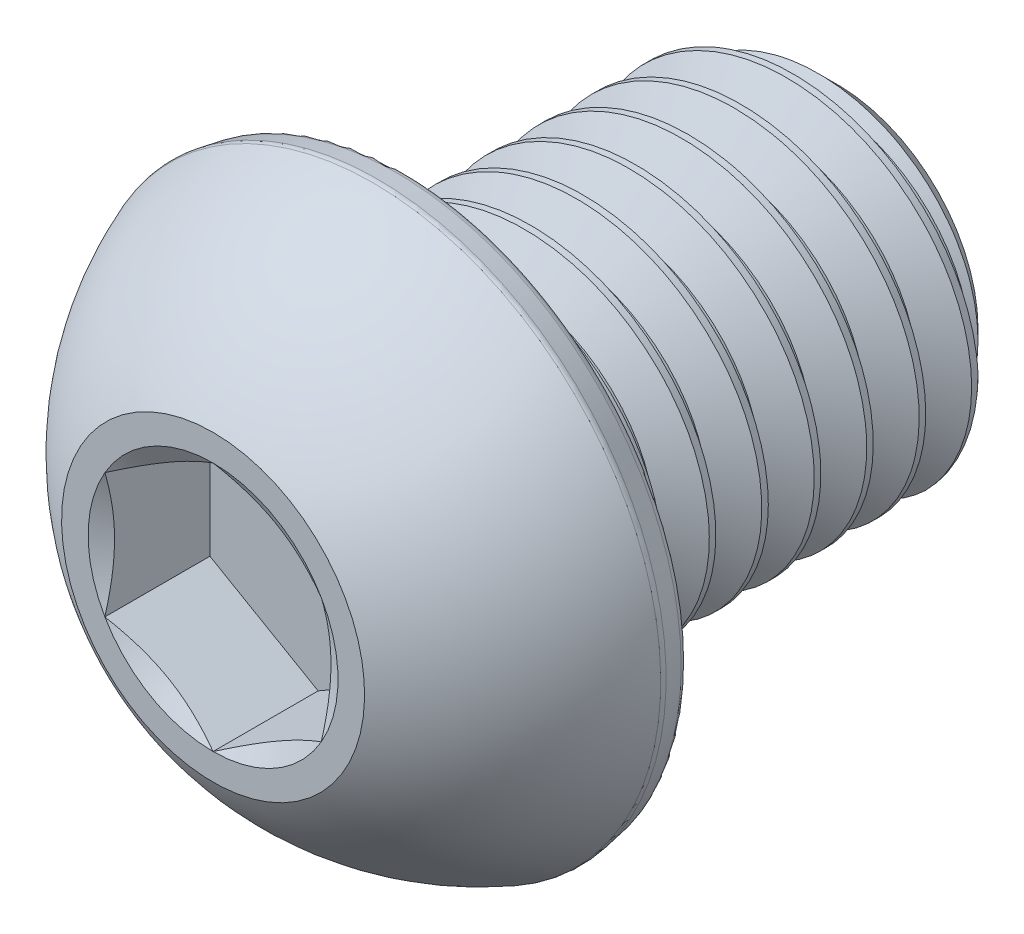
SolidWorks part; units mm, degrees
ref_plane "Front Plane" through (0, 0, 0) normal (0, 0, 1) x (1, 0, 0)
ref_plane "Top Plane" through (0, 0, 0) normal (0, 1, 0) x (1, 0, 0)
ref_plane "Right Plane" through (0, 0, 0) normal (1, 0, 0) x (0, 0, -1)
sketch "Sketch1" plane through (0, 0, 0) normal (1, 0, 0) x (0, 0, -1)
  line L0 (-13.7287, 0) -> (13.7287, 0) construction
  line L1 (-13.7287, 0) -> (-13.7287, 12.7)
  line L2 (-13.7287, 12.7) -> (-5.3213, 12.7)
  line L3 (-5.3213, 12.7) -> (-5.3213, 7.9375)
  line L4 (-5.3213, 7.9375) -> (13.7287, 7.9375)
  line L5 (13.7287, 7.9375) -> (13.7287, 0)
  point P2 (0, 0)
  point P4 (11.4196, 0)
  point P9 (10.2651, 7.9375)
  point P10 (10.2651, -7.9375)
  point P11 (13.7287, -7.9375)
  point P15 (-9.1046, 0)
  dimension "Head Height" = 8.4074
  dimension "Head Diameter" = 25.4
  dimension "Length" = 19.05
  dimension "Screw Size Decimal Equivalent" = 15.875
  dimension "Thread Pitch" = 2.3091
  dimension "D1" = 3.4636
  dimension "D2" = 4.6241
sketch "Sketch2" plane through (0, 0, 0) normal (0, 0, 1) x (1, 0, 0)
  line L0 (0, 7.9375) -> (0, 0) construction
  line L1 (0, 5.4993) -> (-4.7625, 2.7496)
  line L2 (-4.7625, 2.7496) -> (-4.7625, -2.7496)
  line L3 (-4.7625, -2.7496) -> (0, -5.4993)
  line L4 (0, -5.4993) -> (4.7625, -2.7496)
  line L5 (4.7625, -2.7496) -> (4.7625, 2.7496)
  line L6 (4.7625, 2.7496) -> (0, 5.4993)
  circle A0 centre (0, 0) radius 4.7625 construction
  circle A1 centre (0, 0) radius 6.6675
  point P10 (0, 6.6675)
  dimension "D1" = 13.335
  dimension "Drive Size" = 9.525
sketch "Sketch3" plane through (0, 0, 0) normal (1, 0, 0) x (0, 0, -1)
  line L0 (-13.7287, 0) -> (-13.7287, 6.6675)
  line L1 (-13.7287, 0) -> (-13.7287, 12.7) construction
  line L2 (-13.7287, 12.7) -> (-5.3213, 12.7) construction
  line L3 (-6.5824, 12.7) -> (-5.3213, 12.4776)
  line L4 (-5.3213, 12.7) -> (-5.3213, 7.9375) construction
  line L5 (-5.3213, 12.4776) -> (-5.3213, 7.9375)
  line L6 (-13.7287, 0) -> (13.7287, 0) construction
  line L7 (-13.7287, 0) -> (13.7287, 0)
  line L8 (13.7287, 0) -> (13.7287, 6.2057)
  line L9 (13.7287, 7.9375) -> (13.7287, 0) construction
  line L10 (13.7287, 6.2057) -> (11.9969, 7.9375)
  line L11 (-5.3213, 7.9375) -> (13.7287, 7.9375) construction
  line L12 (11.9969, 7.9375) -> (-5.3213, 7.9375)
  arc A0 (-13.7287, 6.6675) -> (-6.5824, 12.7) centre (-1.9811, 0) cw
  dimension "D1" = 1.2611
  dimension "D2" = 10
  dimension "D3" = 45
  dimension "D4" = 1.7318
revolve "Revolve1" add sketch "Sketch3" angle 360 about L7
sketch "Sketch4" plane through (0, 0, 13.7287) normal (0, 0, 1) x (1, 0, 0)
  line L0 (-4.7625, -2.7496) -> (0, -5.4993) construction
  line L1 (-4.7625, 2.7496) -> (-4.7625, -2.7496) construction
  line L2 (0, 5.4993) -> (-4.7625, 2.7496) construction
  line L3 (4.7625, 2.7496) -> (0, 5.4993) construction
  line L4 (4.7625, -2.7496) -> (4.7625, 2.7496) construction
  line L5 (0, -5.4993) -> (4.7625, -2.7496) construction
  line L6 (-4.7625, -2.7496) -> (0, -5.4993)
  line L7 (-4.7625, 2.7496) -> (-4.7625, -2.7496)
  line L8 (0, 5.4993) -> (-4.7625, 2.7496)
  line L9 (4.7625, 2.7496) -> (0, 5.4993)
  line L10 (4.7625, -2.7496) -> (4.7625, 2.7496)
  line L11 (0, -5.4993) -> (4.7625, -2.7496)
extrude "Cut-Extrude1" cut sketch "Sketch4" against normal up to vertex (4.6241 mm away) up to point (0, 0, 9.1046)
sketch "Sketch5" plane through (0, 0, 13.7287) normal (0, 0, 1) x (1, 0, 0)
  circle A0 centre (0, 0) radius 5.4993
extrude "Cut-Extrude2" cut sketch "Sketch5" against normal up to vertex (4.6241 mm away) draft 60 up to point (0, 0, 9.1046)
fillet "Fillet1" radius 0.4204 2 edges at (12.7, 0, 6.5824) (12.4776, 0, 5.3213)
split "Split1" bodies to split 106 resulting bodies 107 108 split by face at (12.1249, 0, 5.3213)
sketch "Sketch6" plane through (0, 0, -13.7287) normal (0, 0, -1) x (-1, 0, 0)
  circle A0 centre (0, 0) radius 7.9375 construction
  circle A1 centre (0, 0) radius 7.9375
curve "Helix/Spiral1" pitch 2.3091 height 21.3591 radius 7.9375 centre (0, 0, -13.7287) axis (0, 0, 1) start towards (0, 1, 0)
sketch "Sketch7" plane through (0, 0, 0) normal (1, 0, 0) x (0, 0, -1)
  line L0 (13.5844, 8.1875) -> (14.7389, 6.1877) construction
  line L1 (14.7389, 6.1877) -> (15.8935, 8.1875) construction
  line L2 (15.8935, 8.1875) -> (13.5844, 8.1875) construction
  line L3 (13.6565, 8.0625) -> (15.8213, 8.0625)
  line L4 (15.8213, 8.0625) -> (14.8832, 6.4377)
  line L5 (14.8832, 6.4377) -> (14.5946, 6.4377)
  line L6 (14.5946, 6.4377) -> (13.6565, 8.0625)
  line L7 (14.7389, 6.4377) -> (14.7389, 6.1877) construction
  line L8 (13.7287, 7.9375) -> (15.7492, 7.9375) construction
  line L9 (14.7389, 8.1875) -> (14.7389, 7.9375) construction
  point P12 (14.7389, 8.0625)
  dimension "D1" = 2.3091
  dimension "D2" = 0.2886
sweep "Cut-Sweep1" cut profiles "Sketch7" path "Helix/Spiral1" align with end faces yes
sketch "Sketch8" plane through (0, 0, 5.3213) normal (0, 0, -1) x (-1, 0, 0)
  circle A0 centre (0, 0) radius 8.1875
extrude "Boss-Extrude1" add sketch "Sketch8" along normal up to vertex (15.5864 mm away) draft 45 up to point (0, 7.9375, -10.2651)
equation "\"D1@Sketch1\"=\"Thread Pitch@Sketch1\"*1.5"
equation "\"D2@Sketch1\"=0.55*\"Head Height@Sketch1\""
equation "\"D1@Sketch2\"=\"Drive Size@Sketch2\"*1.4"
equation "\"D1@Sketch3\"=0.15*\"Head Height@Sketch1\""
equation "\"D4@Sketch3\"=0.75*\"Thread Pitch@Sketch1\""
equation "\"D1@Fillet1\"=.05*\"Head Height@Sketch1\""
equation "\"D4@Helix/Spiral1\"=\"Thread Pitch@Sketch1\""
equation "\"D3@Helix/Spiral1\"=\"Length@Sketch1\"+\"Thread Pitch@Sketch1\""
equation "\"D2@Sketch7\"=\"D1@Sketch7\"/8"
equation "\"D1@Sketch7\"=\"Thread Pitch@Sketch1\""
